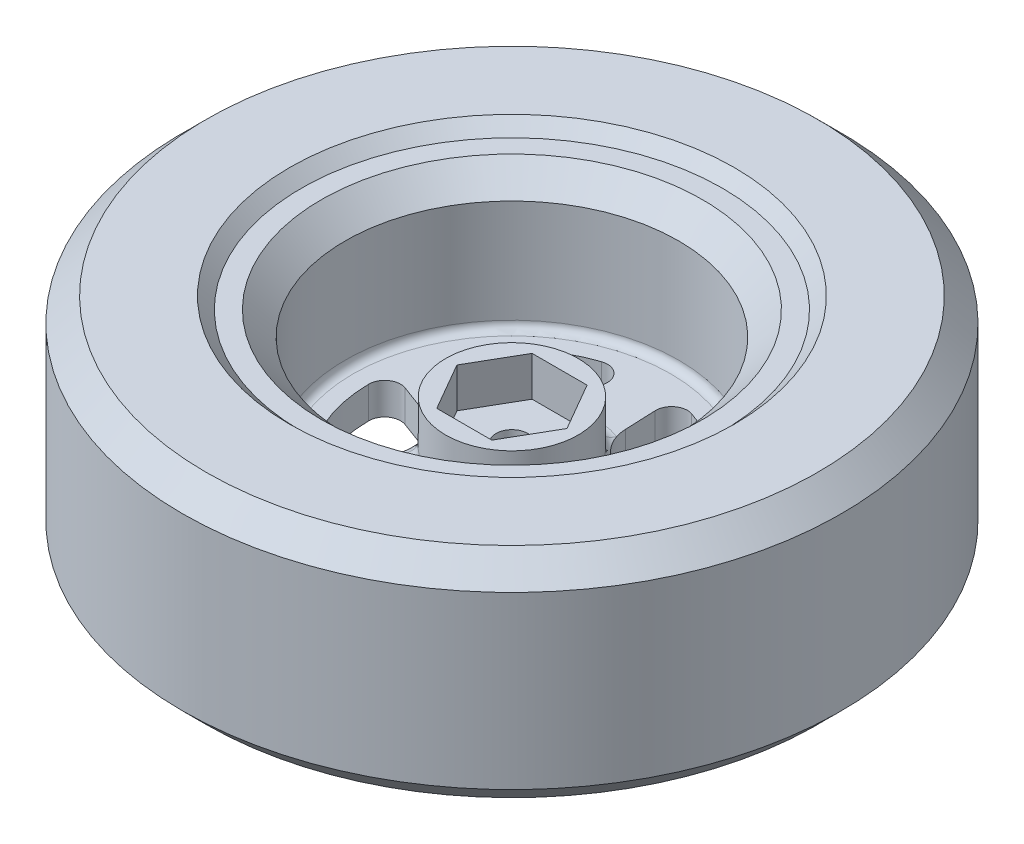
SolidWorks part; units mm, degrees
ref_plane "Спереди" through (0, 0, 0) normal (0, 0, 1) x (1, 0, 0)
ref_plane "Сверху" through (0, 0, 0) normal (0, 1, 0) x (1, 0, 0)
ref_plane "Справа" through (0, 0, 0) normal (1, 0, 0) x (0, 0, -1)
other "Configuration Table"
sketch "Эскиз1" plane through (0, 0, 0) normal (0, 1, 0) x (1, 0, 0)
  circle A0 centre (0, 0) radius 41.5
extrude "Бобышка-Вытянуть1" add sketch "Эскиз1" along normal blind 27.5
sketch "Эскиз2" plane through (0, 27.5, 0) normal (0, 1, 0) x (1, 0, 0)
  line L1 (6.9282, 0) -> (3.4641, 6)
  line L2 (3.4641, 6) -> (-3.4641, 6)
  line L3 (-3.4641, 6) -> (-6.9282, 0)
  line L4 (-6.9282, 0) -> (-3.4641, -6)
  line L5 (-3.4641, -6) -> (3.4641, -6)
  line L6 (3.4641, -6) -> (6.9282, 0)
  circle A0 centre (0, 0) radius 6 construction
extrude "Вырез-Вытянуть1" cut sketch "Эскиз2" against normal blind 16
sketch "Эскиз3" plane through (0, 27.5, 0) normal (0, 1, 0) x (1, 0, 0)
  circle A0 centre (0, 0) radius 25
  circle A1 centre (0, 0) radius 8.35
extrude "Вырез-Вытянуть3" cut sketch "Эскиз3" against normal blind 18.5
sketch "Эскиз4" plane through (0, 27.5, 0) normal (0, 1, 0) x (1, 0, 0)
  circle A0 centre (0, 0) radius 11.6285
extrude "Вырез-Вытянуть4" cut sketch "Эскиз4" against normal blind 11
sketch "Эскиз5" plane through (0, 0, 0) normal (0, -1, 0) x (1, 0, 0)
  circle A0 centre (0, 0) radius 25
extrude "Вырез-Вытянуть6" cut sketch "Эскиз5" against normal blind 5
sketch "Эскиз6" plane through (0, 5, 0) normal (0, -1, 0) x (1, 0, 0)
  circle A0 centre (0, 0) radius 2
extrude "Вырез-Вытянуть7" cut sketch "Эскиз6" against normal blind 10.8
sketch "Эскиз7" plane through (0, 5, 0) normal (0, -1, 0) x (1, 0, 0)
  line L0 (0, 0) -> (0, 25) construction
  line L1 (11.2693, 10.3361) -> (9.1021, 7.0804)
  line L2 (25, 0) -> (0, -25) construction
  line L3 (0, -25) -> (-25, 0) construction
  line L4 (-6.3478, 13.9117) -> (-3.9212, 10.8446)
  line L5 (3.9212, 10.8446) -> (6.3478, 13.9117)
  line L6 (11.5255, -0.3781) -> (15.1924, -1.7382)
  line L7 (13.3126, -7.5237) -> (9.5466, -6.4687)
  line L8 (3.202, -11.0783) -> (3.0416, -14.986)
  line L9 (-3.0416, -14.986) -> (-3.202, -11.0783)
  line L10 (-9.5466, -6.4687) -> (-13.3126, -7.5237)
  line L11 (-15.1924, -1.7382) -> (-11.5255, -0.3781)
  line L12 (-9.1021, 7.0804) -> (-11.2693, 10.3361)
  circle A0 centre (0, 0) radius 25 construction
  circle A1 centre (0, 0) radius 25 construction
  arc A2 (-5.381, 17.0601) -> (5.381, 17.0601) centre (0, 0) cw
  arc A3 (3.9212, 10.8446) -> (-3.9212, 10.8446) centre (0, 13.947) cw
  arc A4 (-6.3478, 13.9117) -> (-5.381, 17.0601) centre (-4.7793, 15.1527) cw
  arc A5 (5.381, 17.0601) -> (6.3478, 13.9117) centre (4.7793, 15.1527) cw
  arc A6 (14.5623, 10.3894) -> (17.8879, 0.1543) centre (0, 0) cw
  arc A7 (11.5255, -0.3781) -> (9.1021, 7.0804) centre (13.2643, 4.3098) cw
  arc A8 (11.2693, 10.3361) -> (14.5623, 10.3894) centre (12.9342, 9.2279) cw
  arc A9 (17.8879, 0.1543) -> (15.1924, -1.7382) centre (15.888, 0.137) cw
  arc A10 (14.3809, -10.639) -> (5.6744, -16.9647) centre (0, 0) cw
  arc A11 (3.202, -11.0783) -> (9.5466, -6.4687) centre (8.1978, -11.2833) cw
  arc A12 (13.3126, -7.5237) -> (14.3809, -10.639) centre (12.7731, -9.4495) cw
  arc A13 (5.6744, -16.9647) -> (3.0416, -14.986) centre (5.0399, -15.068) cw
  arc A14 (-5.6744, -16.9647) -> (-14.3809, -10.639) centre (0, 0) cw
  arc A15 (-9.5466, -6.4687) -> (-3.202, -11.0783) centre (-8.1978, -11.2833) cw
  arc A16 (-3.0416, -14.986) -> (-5.6744, -16.9647) centre (-5.0399, -15.068) cw
  arc A17 (-14.3809, -10.639) -> (-13.3126, -7.5237) centre (-12.7731, -9.4495) cw
  arc A18 (-17.8879, 0.1543) -> (-14.5623, 10.3894) centre (0, 0) cw
  arc A19 (-9.1021, 7.0804) -> (-11.5255, -0.3781) centre (-13.2643, 4.3098) cw
  arc A20 (-15.1924, -1.7382) -> (-17.8879, 0.1543) centre (-15.888, 0.137) cw
  arc A21 (-14.5623, 10.3894) -> (-11.2693, 10.3361) centre (-12.9342, 9.2279) cw
  point P15 (0, 16)
  point P28 (15.2169, 4.9443)
  point P38 (9.4046, -12.9443)
  point P48 (-9.4046, -12.9443)
  point P58 (-15.2169, 4.9443)
  point P64 (0, 0)
  dimension "D1" = 5
  dimension "D2" = 2
  dimension "D3" = 5
extrude "Вырез-Вытянуть8" cut sketch "Эскиз7" against normal blind 10.8
sketch "Эскиз8" plane through (0, 5, 0) normal (0, -1, 0) x (1, 0, 0)
  circle A0 centre (0, 0) radius 25
  circle A1 centre (0, 0) radius 21
extrude "Бобышка-Вытянуть2" add sketch "Эскиз8" along normal blind 4
sketch "Эскиз9" plane through (0, 9, 0) normal (0, 1, 0) x (1, 0, 0)
  circle A0 centre (0, 0) radius 25
  circle A1 centre (0, 0) radius 21
extrude "Бобышка-Вытянуть4" add sketch "Эскиз9" along normal blind 17
chamfer "Фаска1" distance 3 angle 45 1 edges at (0, 27.5, 25)
chamfer "Фаска2" distance 3 angle 45 1 edges at (0, 27.5, 41.5)
chamfer "Фаска3" distance 3 angle 45 1 edges at (0, 0, 41.5)
chamfer "Фаска4" distance 3 angle 45 1 edges at (0, 26, 21)
chamfer "Фаска5" distance 3 angle 45 2 edges at (0, 1, -21) (0, 0, -25)
sketch "Эскиз10" plane through (0, 5, 0) normal (0, -1, 0) x (1, 0, 0)
  circle A0 centre (0, 0) radius 5.5
extrude "Вырез-Вытянуть9" cut sketch "Эскиз10" against normal blind 1
fillet "Скругление2" radius 0.5 2 edges at (0, 6, -5.5) (0, 5, -5.5)
fillet "Скругление3" radius 2 1 edges at (0, 9, 8.35)
fillet "Скругление4" radius 1 1 edges at (0, 9, 21)
fillet "Скругление5" radius 1 1 edges at (0, 5, -21)
